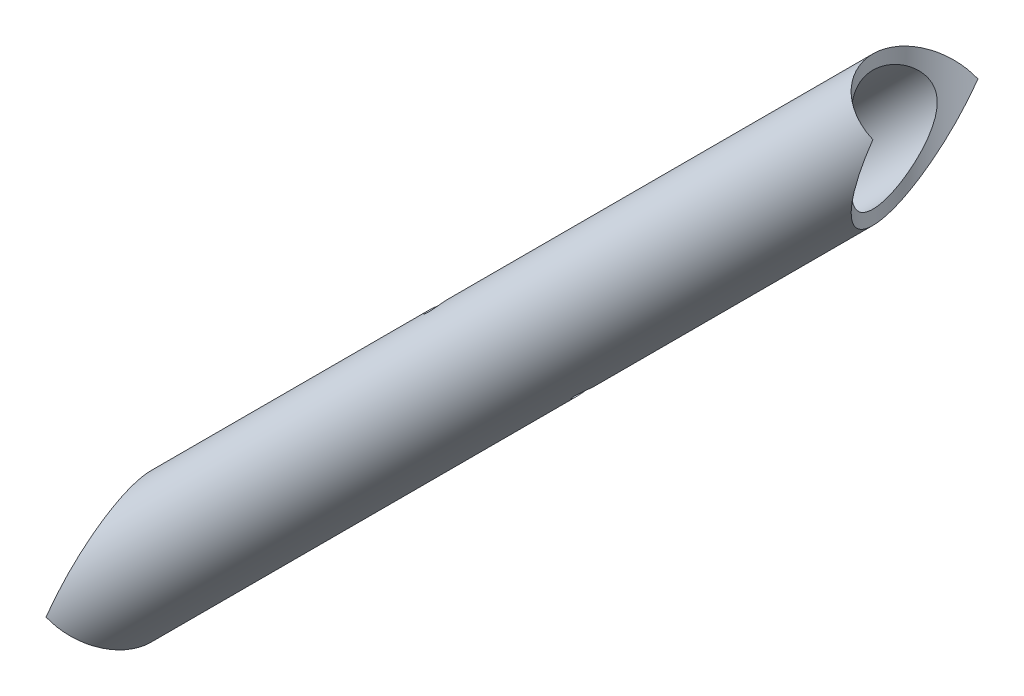
SolidWorks part; units mm, degrees
ref_plane "Front Plane" through (0, 0, 0) normal (0, 0, 1) x (1, 0, 0)
ref_plane "Top Plane" through (0, 0, 0) normal (0, 1, 0) x (1, 0, 0)
ref_plane "Right Plane" through (0, 0, 0) normal (1, 0, 0) x (0, 0, -1)
sketch "Sketch4" plane through (0, 0, 0) normal (0, 0, 1) x (1, 0, 0)
  line L0 (-13.2297, -13.2297) -> (13.2297, 13.2297) construction
  line L1 (0, 0) -> (13.2297, 0) construction
  line L2 (13.2297, 0) -> (13.2297, 13.2297) construction
  line L3 (-116.1685, -101.6204) -> (101.6204, 116.1685)
  line L4 (101.6204, 116.1685) -> (99.9142, 117.8747)
  line L5 (99.9142, 117.8747) -> (-117.8747, -99.9142)
  line L6 (-117.8747, -99.9142) -> (-116.1685, -101.6204)
  line L7 (0, 0) -> (-7.274, 7.274) construction
  dimension "D1" = 12.7
  dimension "D2" = 2.413
  dimension "D3" = 308
  dimension "D4" = 45
revolve "Revolve1" add sketch "Sketch4" angle 360 about L0
sketch "Sketch7" plane through (0, 0, 0) normal (0, 0, 1) x (1, 0, 0)
  line L0 (-113.4139, 0) -> (113.4139, 0) construction
  line L1 (-99.9142, 0) -> (-99.9142, -45.8947) construction
  line L3 (99.9142, 0) -> (99.9142, 59.809) construction
  line L4 (99.9142, 59.809) -> (136.2928, 59.809)
  line L5 (99.9142, 59.809) -> (99.9142, 175.9404)
  line L6 (99.9142, 175.9404) -> (136.2928, 175.9404)
  line L7 (136.2928, 59.809) -> (136.2928, 175.9404)
  line L8 (-99.9142, -45.8947) -> (-119.2687, -45.8947)
  line L9 (-99.9142, -45.8947) -> (-99.9142, -140.4425)
  line L10 (-99.9142, -140.4425) -> (-119.2687, -140.4425)
  line L11 (-119.2687, -45.8947) -> (-119.2687, -140.4425)
  point P13 (65.3531, 0)
  point P14 (-64.5463, -45.8947)
extrude "Cut-Extrude3" cut sketch "Sketch7" against normal blind 152.4 and the other way blind 152.4
sketch "Sketch8" plane through (0, 0, 0) normal (0, 1, 0) x (1, 0, 0)
  line L0 (-99.9142, 0) -> (0, 0) construction
  line L1 (0, 0) -> (99.9142, 0) construction
  line L3 (99.9142, -12.7) -> (99.9142, 12.7) construction
  line L4 (-99.9142, 12.7) -> (-99.9142, -12.7) construction
  circle A0 centre (-99.9142, 0) radius 12.7
  circle A1 centre (99.9142, 0) radius 12.7
  dimension "D3" = 25.4
  dimension "D4" = 25.4
extrude "Cut-Extrude4" cut sketch "Sketch8" against normal blind 152.4 and the other way blind 152.4
sketch "Sketch9" plane through (0, 0, 0) normal (1, 0, 0) x (0, 0, -1)
  circle A0 centre (0, 0) radius 2.5
  dimension "D1" = 5
extrude "Cut-Extrude5" cut sketch "Sketch9" against normal blind 152.4 and the other way blind 152.4
